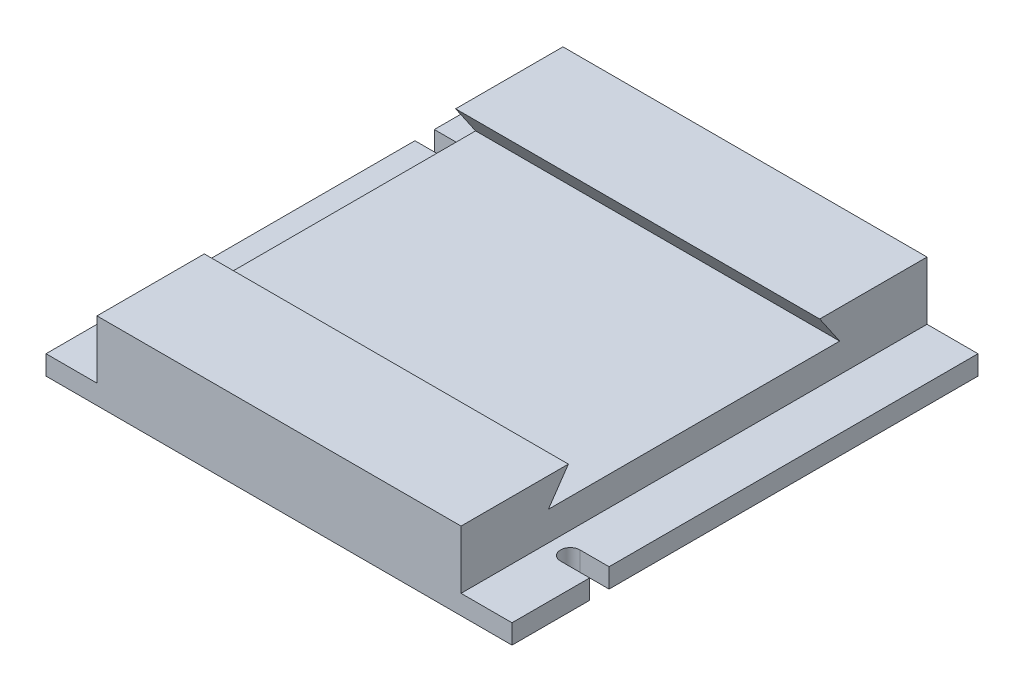
SolidWorks part; units mm, degrees
ref_plane "Спереди" through (0, 0, 0) normal (0, 0, 1) x (1, 0, 0)
ref_plane "Сверху" through (0, 0, 0) normal (0, 1, 0) x (1, 0, 0)
ref_plane "Справа" through (0, 0, 0) normal (1, 0, 0) x (0, 0, -1)
sketch "Эскиз1" plane through (0, 0, 0) normal (1, 0, 0) x (0, 0, -1)
  line L0 (-120, 0) -> (120, 0)
  line L1 (120, 0) -> (120, 40)
  line L6 (120, 40) -> (64.72, 40)
  line L7 (64.72, 40) -> (75, 25)
  line L8 (75, 25) -> (-75, 25)
  line L9 (0, 71.4806) -> (0, -37.2573) construction
  line L10 (-64.72, 40) -> (-75, 25)
  line L11 (-120, 40) -> (-64.72, 40)
  line L16 (-120, 0) -> (-120, 40)
  point P0 (120, 48.3662)
  point P19 (0, 25)
  point P26 (0, 0)
  dimension "D1" = 120
  dimension "D2" = 40
extrude "Бобышка-Вытянуть1" add sketch "Эскиз1" along normal blind 240
sketch "Эскиз2" plane through (0, 0, 0) normal (0, -1, 0) x (1, 0, 0)
  line L5 (240, 80) -> (240, 70)
  line L6 (240, 120) -> (240, -120) construction
  line L7 (240, 70) -> (225, 70)
  line L9 (225, 80) -> (240, 80)
  line L10 (0, 0) -> (240, 0) construction
  line L11 (0, -80) -> (0, -70)
  line L12 (0, -70) -> (15, -70)
  line L13 (15, -80) -> (0, -80)
  arc A0 (225, 80) -> (225, 70) centre (225, 75) ccw
  arc A1 (15, -80) -> (15, -70) centre (15, -75) ccw
  point P9 (120, 0)
  point P10 (120, 0)
  point P19 (120, 0)
  dimension "D1" = 2
extrude "Вырез-Вытянуть1" cut sketch "Эскиз2" against normal through all
sketch "Эскиз3" plane through (0, 40, 0) normal (0, 1, 0) x (1, 0, 0)
  line L1 (0, 120) -> (26.2453, 120)
  line L2 (0, 120) -> (0, -120)
  line L3 (0, -120) -> (26.2453, -120)
  line L4 (26.2453, 120) -> (26.2453, -120)
  line L5 (120, 120) -> (120, -120) construction
  line L7 (213.7547, 120) -> (213.7547, -120)
  line L8 (240, -120) -> (213.7547, -120)
  line L9 (240, 120) -> (240, -120)
  line L10 (240, 120) -> (213.7547, 120)
  point P5 (120.6421, 120)
extrude "Вырез-Вытянуть2" cut sketch "Эскиз3" against normal blind 30
